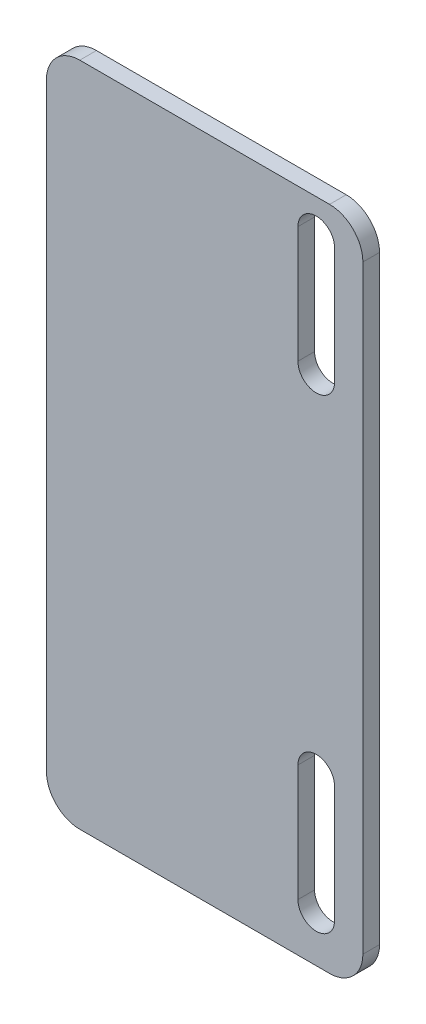
SolidWorks part; units mm, degrees
ref_plane "Спереди" through (0, 0, 0) normal (0, 0, 1) x (1, 0, 0)
ref_plane "Сверху" through (0, 0, 0) normal (0, 1, 0) x (1, 0, 0)
ref_plane "Справа" through (0, 0, 0) normal (1, 0, 0) x (0, 0, -1)
sketch "Эскиз1" plane through (0, 0, 0) normal (0, 0, 1) x (1, 0, 0)
  line L1 (0, 0) -> (19, 0)
  line L2 (0, 0) -> (0, 40)
  line L3 (0, 40) -> (19, 40)
  line L4 (19, 0) -> (19, 40)
  dimension "D1" = 19
  dimension "D2" = 40
extrude "Бобышка-Вытянуть1" add sketch "Эскиз1" along normal blind 1
fillet "Скругление1" radius 2 4 edges at (19, 0, 0.5) (0, 0, 0.5) (0, 40, 0.5) (19, 40, 0.5)
sketch "Эскиз3" plane through (0, 0, 1) normal (0, 0, 1) x (1, 0, 0)
  line L0 (16.2, 2.8934) -> (16.2, 9.8934) construction
  line L1 (17, 6.3934) -> (15.4, 6.3934) construction
  line L2 (17, 9.8934) -> (17, 2.8934) construction
  line L3 (15.4, 9.8934) -> (15.4, 2.8934) construction
  line L4 (15.1, 2.8934) -> (15.1, 9.8934)
  line L5 (17.3, 2.8934) -> (17.3, 9.8934)
  line L6 (17, 34.3934) -> (15.4, 34.3934) construction
  line L7 (17, 37.8934) -> (17, 30.8934) construction
  line L8 (15.4, 37.8934) -> (15.4, 30.8934) construction
  line L9 (16.2, 30.8934) -> (16.2, 37.8934) construction
  line L10 (15.1, 30.8934) -> (15.1, 37.8934)
  line L11 (17.3, 30.8934) -> (17.3, 37.8934)
  arc A0 (15.1, 2.8934) -> (17.3, 2.8934) centre (16.2, 2.8934) ccw
  arc A1 (17.3, 9.8934) -> (15.1, 9.8934) centre (16.2, 9.8934) ccw
  arc A2 (15.1, 30.8934) -> (17.3, 30.8934) centre (16.2, 30.8934) ccw
  arc A3 (17.3, 37.8934) -> (15.1, 37.8934) centre (16.2, 37.8934) ccw
  point P6 (16.2, 6.3934)
  point P21 (16.2, 34.3934)
  dimension "D1" = 2.2
  dimension "D2" = 7
  dimension "D3" = 2.2
  dimension "D4" = 7
extrude "Вырез-Вытянуть1" cut sketch "Эскиз3" against normal through all
